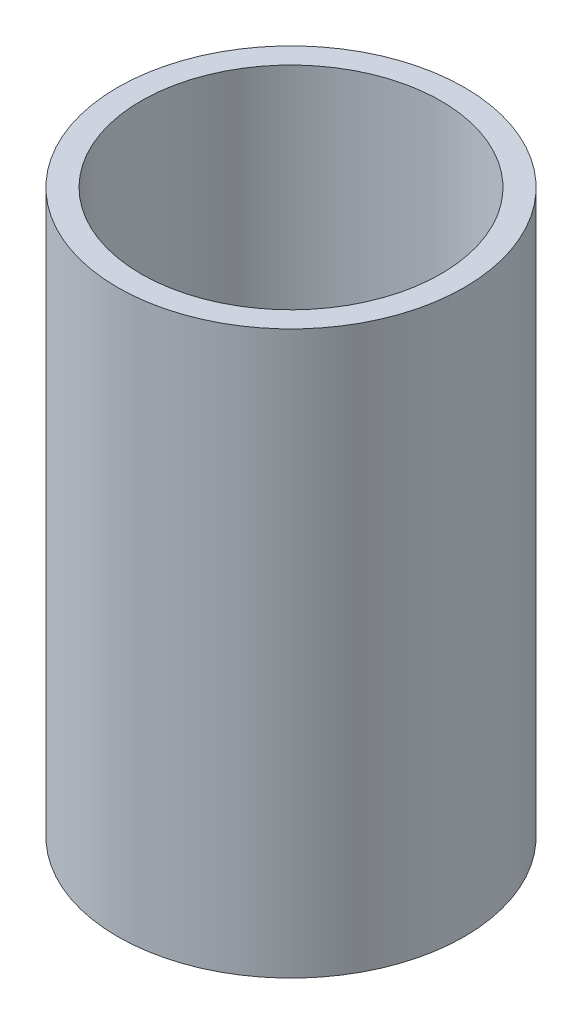
SolidWorks part; units mm, degrees
ref_plane "Front Plane" through (0, 0, 0) normal (0, 0, 1) x (1, 0, 0)
ref_plane "Top Plane" through (0, 0, 0) normal (0, 1, 0) x (1, 0, 0)
ref_plane "Right Plane" through (0, 0, 0) normal (1, 0, 0) x (0, 0, -1)
sketch "Sketch1" plane through (0, 0, 0) normal (0, 1, 0) x (1, 0, 0)
  circle A0 centre (0, 0) radius 8
  circle A1 centre (0, 0) radius 9.25
  circle A2 centre (0, 0) radius 2
  dimension "D1" = 16
  dimension "D2" = 1.25
  dimension "D3" = 4
extrude "Boss-Extrude1" add sketch "Sketch1" along normal blind 30 contours A1
extrude "Cut-Extrude1" cut sketch "Sketch1<3>" against normal offset from surface (28 mm away) 2 from surface contours A0 up to face at (0, 0, 9.25) starting at face at (0, 30, 9.25)
sketch "Sketch1<3>" plane through (0, 0, 0) normal (0, 1, 0) x (1, 0, 0) same geometry as "Sketch1"
extrude "Cut-Extrude3" cut sketch "Sketch1<4>" against normal through all both and the other way through all contours A2
sketch "Sketch1<4>" plane through (0, 0, 0) normal (0, 1, 0) x (1, 0, 0) same geometry as "Sketch1"
